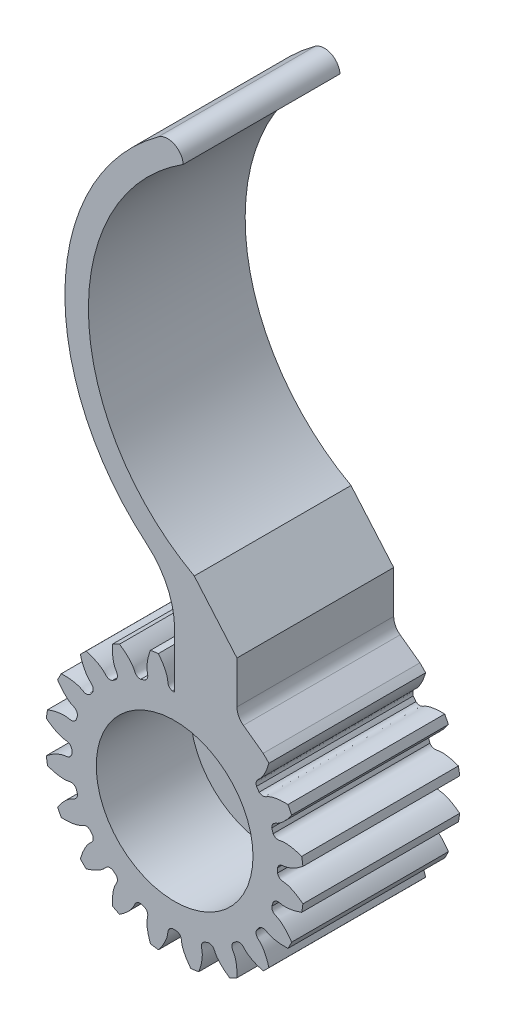
SolidWorks part; units mm, degrees
material "聚脂树脂"
ref_plane "前视基准面" through (0, 0, 0) normal (0, 0, 1) x (1, 0, 0)
ref_plane "上视基准面" through (0, 0, 0) normal (0, 1, 0) x (1, 0, 0)
ref_plane "右视基准面" through (0, 0, 0) normal (1, 0, 0) x (0, 0, -1)
other "Configuration Table"
sketch "草图1" plane through (0, 0, 0) normal (0, 0, 1) x (1, 0, 0)
  circle A0 centre (0, 0) radius 16.5
extrude "凸台-拉伸1" add sketch "草图1" along normal blind 20
ref_axis "基准轴1" through (0, 0, -1.5) along (0, 0, 1)
sketch "草图2" plane through (0, 0, 0) normal (0, 0, 1) x (1, 0, 0)
  line L0 (0, 0) -> (0, 16.5) construction
  circle A0 centre (0, 0) radius 16.5 construction
  arc A1 (0.29, 13.1218) -> (-0.29, 13.1218) centre (0, 0) ccw
  arc A2 (4.7717, 18.7474) -> (-4.7717, 18.7474) centre (0, 0) ccw
  spline S0 degree 3 poles (0.29, 13.1218) (0.9168, 13.3402) (0.8356, 13.7807) (0.9193, 14.205) (0.9283, 14.2463) (0.9395, 14.293) (0.9529, 14.3448) (0.969, 14.4018) (0.9878, 14.4638) (1.0095, 14.5309) (1.0345, 14.6028) (1.0629, 14.6795) (1.0948, 14.7608) (1.1305, 14.8467) (1.1702, 14.9371) (1.2141, 15.0317) (1.2623, 15.1305) (1.315, 15.2334) (1.3725, 15.3401) (1.4349, 15.4506) (1.5023, 15.5646) (1.575, 15.6821) (1.653, 15.8029) (1.7366, 15.9267) (1.826, 16.0534) (1.9211, 16.1829) (2.0223, 16.3149) (2.1296, 16.4493) (2.2432, 16.5859) (2.3632, 16.7244) (2.4897, 16.8646) (2.6229, 17.0065) (2.7628, 17.1496) (2.9095, 17.2939) (3.0632, 17.4391) (3.224, 17.585) (3.3918, 17.7313) (3.567, 17.8779) (3.7493, 18.0245) (3.9391, 18.1709) (4.1363, 18.3167) (4.4122, 18.5125) (4.6259, 18.6545) (4.7717, 18.7474) knots 0 0 0 0 0.165916 0.170906 0.176664 0.183189 0.190482 0.198542 0.207371 0.216967 0.22733 0.238462 0.250361 0.263027 0.276462 0.290664 0.305634 0.321371 0.337876 0.355149 0.37319 0.391998 0.411574 0.431917 0.453028 0.474907 0.497554 0.520968 0.54515 0.570099 0.595817 0.622302 0.649554 0.677575 0.706363 0.735918 0.766242 0.797333 0.829191 0.861818 0.895212 0.929373 1 1 1 1
  spline S1 degree 3 poles (-0.29, 13.1218) (-0.9168, 13.3402) (-0.8356, 13.7807) (-0.9193, 14.205) (-0.9283, 14.2463) (-0.9395, 14.293) (-0.9529, 14.3448) (-0.969, 14.4018) (-0.9878, 14.4638) (-1.0095, 14.5309) (-1.0345, 14.6028) (-1.0629, 14.6795) (-1.0948, 14.7608) (-1.1305, 14.8467) (-1.1702, 14.9371) (-1.2141, 15.0317) (-1.2623, 15.1305) (-1.315, 15.2334) (-1.3725, 15.3401) (-1.4349, 15.4506) (-1.5023, 15.5646) (-1.575, 15.6821) (-1.653, 15.8029) (-1.7366, 15.9267) (-1.826, 16.0534) (-1.9211, 16.1829) (-2.0223, 16.3149) (-2.1296, 16.4493) (-2.2432, 16.5859) (-2.3632, 16.7244) (-2.4897, 16.8646) (-2.6229, 17.0065) (-2.7628, 17.1496) (-2.9095, 17.2939) (-3.0632, 17.4391) (-3.224, 17.585) (-3.3918, 17.7313) (-3.567, 17.8779) (-3.7493, 18.0245) (-3.9391, 18.1709) (-4.1363, 18.3167) (-4.4122, 18.5125) (-4.6259, 18.6545) (-4.7717, 18.7474) knots 0 0 0 0 0.165916 0.170906 0.176664 0.183189 0.190482 0.198542 0.207371 0.216967 0.22733 0.238462 0.250361 0.263027 0.276462 0.290664 0.305634 0.321371 0.337876 0.355149 0.37319 0.391998 0.411574 0.431917 0.453028 0.474907 0.497554 0.520968 0.54515 0.570099 0.595817 0.622302 0.649554 0.677575 0.706363 0.735918 0.766242 0.797333 0.829191 0.861818 0.895212 0.929373 1 1 1 1
extrude "切除-拉伸1" cut sketch "草图2" along normal through all
pattern_circular "阵列(圆周)1" count 20 over 360 about axis through (0, 0, -1.5) along (0, 0, 1) of "切除-拉伸1"
sketch "草图3" plane through (0, 0, 0) normal (0, 0, 1) x (1, 0, 0)
  circle A0 centre (0, 0) radius 15 construction
  dimension "Dn" = 30
sketch "草图4" plane through (0, 0, 0) normal (0, 0, -1) x (-1, 0, 0)
  line L0 (0, 0) -> (67.6919, 0) construction
  line L1 (0, 13.125) -> (0, 76.7697) construction
  line L2 (-15, 0) -> (-15, 67.6903) construction
  line L3 (-7.9502, 14.4584) -> (-7.9502, 25)
  line L4 (0, 13.125) -> (0, 25.2067)
  line L5 (-2.1023, 76) -> (-1.1024, 72)
  line L6 (-7.9502, 14.4584) -> (-11.294, 12.029)
  circle A2 centre (-15, 50.026) radius 26 construction
  circle A3 centre (-15, 50.026) radius 29 construction
  arc A4 (-7.9502, 25) -> (-1.1024, 72) centre (-15, 50.026) ccw
  arc A5 (0, 25.2067) -> (-2.1023, 76) centre (-15, 50.026) ccw
  arc A6 (0.29, 13.1218) -> (-0.29, 13.1218) centre (0, 0) ccw construction
  arc A7 (-2.0665, 16.3701) -> (-3.0932, 16.2075) centre (0, 0) ccw construction
  arc A8 (-3.7791, 12.5692) -> (-4.3306, 12.39) centre (0, 0) ccw construction
  arc A9 (-7.024, 14.9303) -> (-7.9502, 14.4584) centre (0, 0) ccw construction
  arc A10 (0, 13.125) -> (-0.29, 13.1218) centre (0, 0) ccw
  arc A11 (-2.0665, 16.3701) -> (-3.0932, 16.2075) centre (0, 0) ccw
  arc A12 (-3.7791, 12.5692) -> (-4.3306, 12.39) centre (0, 0) ccw
  arc A13 (-7.024, 14.9303) -> (-7.9502, 14.4584) centre (0, 0) ccw
  arc A14 (-7.4782, 10.7862) -> (-7.9474, 10.4453) centre (0, 0) ccw construction
  arc A15 (-7.4782, 10.7862) -> (-7.9474, 10.4453) centre (0, 0) ccw
  circle A16 centre (0, 0) radius 12.5
  spline S2 degree 3 poles (1929.2589, 538.6725) (-25.8757, -1.4089) (0.1295, 8.8889) (-0.9224, 14.2207) (-0.9359, 14.2793) (-0.9529, 14.3448) (-0.969, 14.4018) (-0.9951, 14.4881) (-1.0357, 14.6084) (-1.0961, 14.7664) (-1.1716, 14.9426) (-1.2638, 15.1361) (-1.3741, 15.3456) (-1.5041, 15.5702) (-1.6549, 15.8084) (-1.7965, 16.0133) (-1.9211, 16.1829) (-18.5962, 37.9418) (-139.7723, -22.1232) (1994.2672, 135.3242) knots -2.036559 -2.036559 -2.036559 -2.036559 0.165916 0.170906 0.183189 0.190482 0.198542 0.207371 0.22733 0.250361 0.276462 0.305634 0.337876 0.37319 0.411574 0.453028 0.474907 0.497554 11.650216 11.650216 11.650216 11.650216 only from (-0.29, 13.1218) to (-2.0665, 16.3701) construction
  spline S3 degree 3 poles (-2001.2932, -83.8658) (25.0446, 6.6561) (-2.87, 8.4138) (-3.5171, 13.8097) (-3.5224, 13.8696) (-3.5265, 13.9372) (-3.5289, 13.9963) (-3.5307, 14.0865) (-3.5293, 14.2134) (-3.5206, 14.3824) (-3.5033, 14.5733) (-3.4754, 14.7858) (-3.4352, 15.0192) (-3.381, 15.2729) (-3.3111, 15.5461) (-3.2398, 15.7847) (-3.1737, 15.9845) (5.9613, 41.8314) (139.7678, 22.1516) (-1938.4783, -487.5615) knots -1.54399 -1.54399 -1.54399 -1.54399 0.658484 0.663474 0.675757 0.68305 0.691111 0.699939 0.719899 0.742929 0.76903 0.798202 0.830445 0.865758 0.904142 0.945597 0.967475 0.990122 12.142784 12.142784 12.142784 12.142784 only from (-3.7791, 12.5692) to (-3.0932, 16.2075) construction
  spline S4 degree 3 poles (1668.3753, 1108.4817) (-24.1739, -9.3359) (-2.6237, 8.4938) (-5.2717, 13.2396) (-5.3027, 13.2912) (-5.3391, 13.3482) (-5.3719, 13.3975) (-5.4235, 13.4715) (-5.4992, 13.5733) (-5.6055, 13.705) (-5.7318, 13.8492) (-5.8792, 14.0047) (-6.0489, 14.1699) (-6.2419, 14.3433) (-6.459, 14.5233) (-6.6569, 14.6744) (-6.8279, 14.7972) (-29.4107, 30.3383) (-126.0949, -64.2324) (1854.8434, 744.9634) knots -2.036559 -2.036559 -2.036559 -2.036559 0.165916 0.170906 0.183189 0.190482 0.198542 0.207371 0.22733 0.250361 0.276462 0.305634 0.337876 0.37319 0.411574 0.453028 0.474907 0.497554 11.650216 11.650216 11.650216 11.650216 only from (-4.3306, 12.39) to (-7.024, 14.9303) construction
  spline S5 degree 3 poles (-0.29, 13.1218) (-0.9168, 13.3402) (-0.8356, 13.7807) (-0.9224, 14.2207) (-0.9359, 14.2793) (-0.9529, 14.3448) (-0.969, 14.4018) (-0.9951, 14.4881) (-1.0357, 14.6084) (-1.0961, 14.7664) (-1.1716, 14.9426) (-1.2638, 15.1361) (-1.3741, 15.3456) (-1.5041, 15.5702) (-1.6549, 15.8084) (-1.828, 16.0589) (-1.969, 16.2466) (-2.0515, 16.3512) (-2.0665, 16.3701) knots 0 0 0 0 0.165916 0.170906 0.183189 0.190482 0.198542 0.207371 0.22733 0.250361 0.276462 0.305634 0.337876 0.37319 0.411574 0.453028 0.497554 0.507432 0.507432 0.507432 0.507432
  spline S6 degree 3 poles (-3.7791, 12.5692) (-3.2504, 12.9706) (-3.4637, 13.3644) (-3.5171, 13.8097) (-3.5224, 13.8696) (-3.5265, 13.9372) (-3.5289, 13.9963) (-3.5307, 14.0865) (-3.5293, 14.2134) (-3.5206, 14.3824) (-3.5033, 14.5733) (-3.4754, 14.7858) (-3.4352, 15.0192) (-3.381, 15.2729) (-3.3111, 15.5461) (-3.224, 15.8378) (-3.1479, 16.0599) (-3.1017, 16.1848) (-3.0932, 16.2075) knots 0.492568 0.492568 0.492568 0.492568 0.658484 0.663474 0.675757 0.68305 0.691111 0.699939 0.719899 0.742929 0.76903 0.798202 0.830445 0.865758 0.904142 0.945597 0.990122 1 1 1 1
  spline S7 degree 3 poles (-4.3306, 12.39) (-4.9943, 12.404) (-5.0532, 12.848) (-5.2717, 13.2396) (-5.3027, 13.2912) (-5.3391, 13.3482) (-5.3719, 13.3975) (-5.4235, 13.4715) (-5.4992, 13.5733) (-5.6055, 13.705) (-5.7318, 13.8492) (-5.8792, 14.0047) (-6.0489, 14.1699) (-6.2419, 14.3433) (-6.459, 14.5233) (-6.701, 14.7081) (-6.8931, 14.843) (-7.0039, 14.9169) (-7.024, 14.9303) knots 0 0 0 0 0.165916 0.170906 0.183189 0.190482 0.198542 0.207371 0.22733 0.250361 0.276462 0.305634 0.337876 0.37319 0.411574 0.453028 0.497554 0.507432 0.507432 0.507432 0.507432
  spline S8 degree 3 poles (-1877.4269, -698.1947) (21.762, 14.0695) (-5.3295, 7.1151) (-7.6124, 12.047) (-7.636, 12.1023) (-7.6607, 12.1653) (-7.6812, 12.2208) (-7.7108, 12.3061) (-7.7487, 12.4272) (-7.7927, 12.5905) (-7.8352, 12.7775) (-7.8743, 12.9882) (-7.9082, 13.2226) (-7.9351, 13.4806) (-7.9531, 13.762) (-7.959, 14.011) (-7.9578, 14.2215) (-7.257, 41.6261) (126.0819, 64.2581) (-1692.9376, -1062.7213) knots -1.54399 -1.54399 -1.54399 -1.54399 0.658484 0.663474 0.675757 0.68305 0.691111 0.699939 0.719899 0.742929 0.76903 0.798202 0.830445 0.865758 0.904142 0.945597 0.967475 0.990122 12.142784 12.142784 12.142784 12.142784 only from (-7.4782, 10.7862) to (-7.9502, 14.4584) construction
  spline S9 degree 3 poles (1244.1795, 1569.7851) (-20.1057, -16.3491) (-5.12, 7.2674) (-9.105, 10.9626) (-9.1503, 11.0021) (-9.2026, 11.0451) (-9.2491, 11.0817) (-9.321, 11.1362) (-9.4245, 11.2097) (-9.5662, 11.302) (-9.7309, 11.4002) (-9.9192, 11.5025) (-10.1316, 11.6072) (-10.3687, 11.7125) (-10.6308, 11.8165) (-10.8658, 11.8991) (-11.0663, 11.963) (-37.3463, 19.765) (-100.0745, -100.0541) (1533.8545, 1281.6804) knots -2.036559 -2.036559 -2.036559 -2.036559 0.165916 0.170906 0.183189 0.190482 0.198542 0.207371 0.22733 0.250361 0.276462 0.305634 0.337876 0.37319 0.411574 0.453028 0.474907 0.497554 11.650216 11.650216 11.650216 11.650216 only from (-7.9474, 10.4453) to (-11.294, 12.029) construction
  spline S10 degree 3 poles (-7.4782, 10.7862) (-7.0995, 11.3313) (-7.424, 11.64) (-7.6124, 12.047) (-7.636, 12.1023) (-7.6607, 12.1653) (-7.6812, 12.2208) (-7.7108, 12.3061) (-7.7487, 12.4272) (-7.7927, 12.5905) (-7.8352, 12.7775) (-7.8743, 12.9882) (-7.9082, 13.2226) (-7.9351, 13.4806) (-7.9531, 13.762) (-7.9603, 14.0664) (-7.9566, 14.3011) (-7.9513, 14.4342) (-7.9502, 14.4584) knots 0.492568 0.492568 0.492568 0.492568 0.658484 0.663474 0.675757 0.68305 0.691111 0.699939 0.719899 0.742929 0.76903 0.798202 0.830445 0.865758 0.904142 0.945597 0.990122 1 1 1 1
  spline S11 degree 3 poles (-7.9474, 10.4453) (-8.5829, 10.2536) (-8.7761, 10.6576) (-9.105, 10.9626) (-9.1503, 11.0021) (-9.2026, 11.0451) (-9.2491, 11.0817) (-9.321, 11.1362) (-9.4245, 11.2097) (-9.5662, 11.302) (-9.7309, 11.4002) (-9.9192, 11.5025) (-10.1316, 11.6072) (-10.3687, 11.7125) (-10.6308, 11.8165) (-10.9181, 11.9175) (-11.1425, 11.9864) (-11.2707, 12.0225) (-11.294, 12.029) knots 0 0 0 0 0.165916 0.170906 0.183189 0.190482 0.198542 0.207371 0.22733 0.250361 0.276462 0.305634 0.337876 0.37319 0.411574 0.453028 0.497554 0.507432 0.507432 0.507432 0.507432
  dimension "D7" = 47
  dimension "D4" = 52
  dimension "D5" = 58
  dimension "D3" = 25
  dimension "D1" = 15
  dimension "D2" = 25
  dimension "D6" = 4
extrude "凸台-拉伸2" add sketch "草图4" against normal blind 20 contours S7 A12 S6 A11 S5 A10 L4 A5 L5 A4 L3 A13 | S11 A15 S10 L6 region at (8.8549, 12.1877, 0) region at (7.2773, 19.7292, 0)
fillet "圆角1" radius 10 1 edges at (0, 25.2067, 10)
fillet "圆角2" radius 2 2 edges at (2.1023, 76, 10) (7.9502, 14.4584, 10)
sketch "草图5" plane through (0, 0, 0) normal (0, 0, -1) x (-1, 0, 0)
  line L0 (0, 0) -> (47.9973, 0) construction
  line L1 (0, 0) -> (0, 54.3289) construction
sketch "草图7" plane through (0, 0, 20) normal (0, 0, 1) x (1, 0, 0)
  line L0 (0, 0) -> (42.9933, 0) construction
  line L1 (0, 0) -> (0, 51.6895) construction
  circle A0 centre (0, 0) radius 10
  dimension "D1" = 20
extrude "切除-拉伸2" cut sketch "草图7" against normal blind 12
sketch "草图8" plane through (0, 0, 8) normal (0, 0, 1) x (1, 0, 0)
  line L0 (0, 0) -> (25.4464, 0) construction
  line L1 (0, 0) -> (0, 31.9913) construction
  circle A0 centre (0, 0) radius 3.5
  circle A1 centre (0, 7) radius 1.5
  circle A2 centre (7, 0) radius 1.5
  circle A3 centre (0, -7) radius 1.5
  circle A4 centre (-7, 0) radius 1.5
  dimension "D1" = 3
  dimension "D2" = 7
  dimension "D4" = 3
  dimension "D3" = 7
  dimension "D5" = 7
extrude "切除-拉伸3" cut sketch "草图8" against normal blind 10
chamfer "倒角1" distance 5 angle 45 1 edges at (7.9502, 25, 10) first distance on face at (7.9502, 20.2387, 10)
sketch "草图9" plane through (0, 0, 20) normal (0, 0, -1) x (-1, 0, 0)
  line L0 (-2.5042, 27.2257) -> (-7.9502, 20.8839)
  line L1 (-7.9502, 20.8839) -> (0, 20.0927)
  arc A0 (3.5897, 27.7679) -> (0, 20.0927) centre (10, 20.0927) ccw construction
  arc A1 (3.5897, 27.7679) -> (2.0694, 73.4703) centre (-15, 50.026) ccw construction
  arc A2 (-2.5042, 27.2257) -> (-1.1024, 72) centre (-15, 50.026) ccw construction
  arc A3 (2.0694, 73.4703) -> (-1.1024, 72) centre (0.8922, 71.8534) ccw construction
  arc A4 (3.5897, 27.7679) -> (0, 20.0927) centre (10, 20.0927) ccw
  arc A5 (3.5897, 27.7679) -> (2.0694, 73.4703) centre (-15, 50.026) ccw
  arc A6 (-2.5042, 27.2257) -> (-1.1024, 72) centre (-15, 50.026) ccw
  arc A7 (2.0694, 73.4703) -> (-1.1024, 72) centre (0.8922, 71.8534) ccw
sketch "草图10" plane through (0, 0, 0) normal (0, 0, -1) x (-1, 0, 0)
  circle A0 centre (0, 0) radius 10
  circle A1 centre (-7, 0) radius 1.5 construction
  circle A2 centre (0, -7) radius 1.5 construction
  circle A3 centre (0, 0) radius 3.5 construction
  circle A4 centre (7, 0) radius 1.5 construction
  circle A5 centre (0, 7) radius 1.5 construction
  circle A6 centre (-7, 0) radius 1.5
  circle A7 centre (0, -7) radius 1.5
  circle A8 centre (0, 0) radius 3.5
  circle A9 centre (7, 0) radius 1.5
  circle A10 centre (0, 7) radius 1.5
  dimension "D1" = 20
extrude "凸台-拉伸3" add sketch "草图10" along normal blind 2
fillet "圆角3" radius 2 1 edges at (10, 0, 0)
